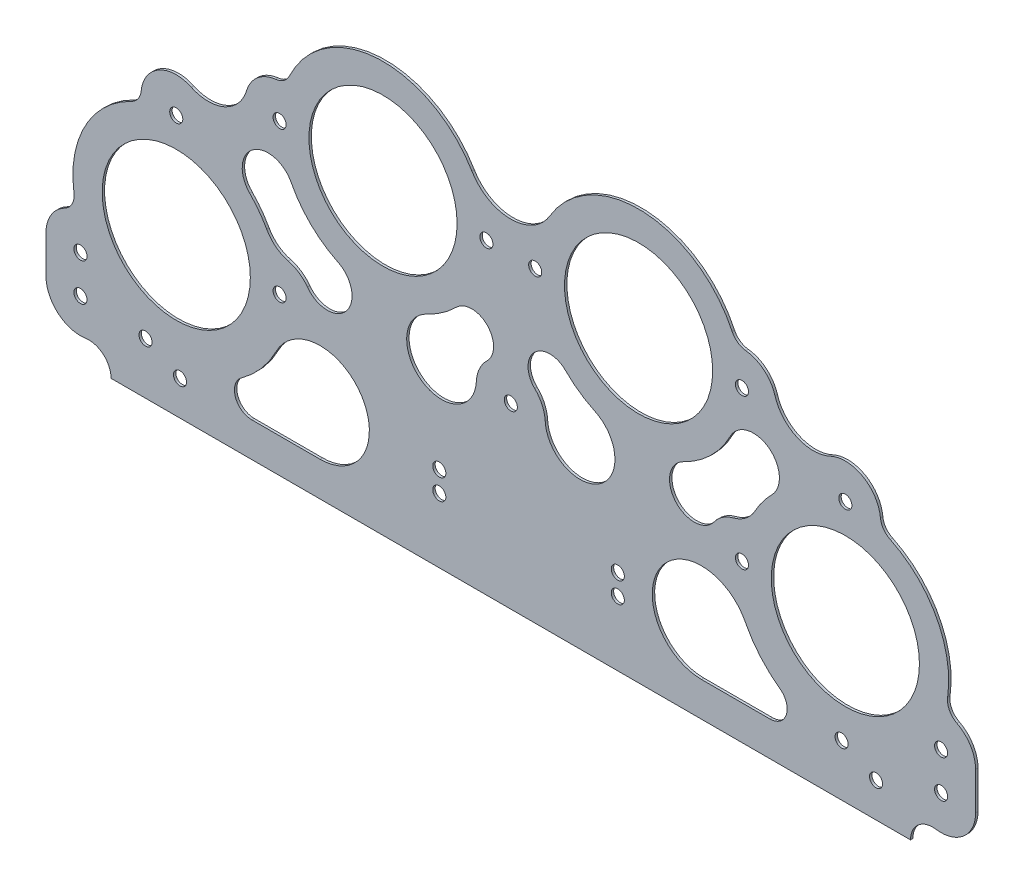
SolidWorks part; units mm, degrees
ref_plane "Front Plane" through (0, 0, 0) normal (0, 0, 1) x (1, 0, 0)
ref_plane "Top Plane" through (0, 0, 0) normal (0, 1, 0) x (1, 0, 0)
ref_plane "Right Plane" through (0, 0, 0) normal (1, 0, 0) x (0, 0, -1)
sketch "Model" plane through (0, 0, 0) normal (0, 0, 1) x (1, 0, 0)
  line L0 (-55.1744, -8.9726) -> (-75.0448, -8.9726)
  line L1 (75.3558, -8.9726) -> (55.4854, -8.9726)
  line L2 (-134.7255, -2.7113) -> (-134.7255, 8.1935)
  line L3 (116.1555, -18.9726) -> (-115.8445, -18.9726)
  line L4 (135.0365, -2.7113) -> (135.0365, 8.1935)
  arc A0 (-70.6765, 41.0853) -> (-75.6107, 47.6717) centre (-96.9265, 26.5616) ccw
  arc A1 (-63.5904, 56.405) -> (-75.6107, 47.6717) centre (-70.2705, 52.9604) ccw
  arc A2 (-63.5904, 56.405) -> (-49.9598, 43.1331) centre (-36.9265, 70.1542) ccw
  arc A3 (-58.8518, 32.4606) -> (-49.9598, 43.1331) centre (-53.0703, 36.6842) ccw
  arc A4 (-58.8518, 32.4606) -> (-64.4265, 36.2441) centre (-66.9265, 26.5616) ccw
  arc A5 (-70.6765, 41.0853) -> (-64.4265, 36.2441) centre (-61.9265, 45.9265) ccw
  arc A6 (-77.9573, 0.0915) -> (-67.9041, 11.7901) centre (-96.9265, 26.5616) ccw
  arc A7 (-55.1744, -8.9726) -> (-67.9041, 11.7901) centre (-55.1744, 5.3111) ccw
  arc A8 (-77.9573, 0.0915) -> (-75.0448, -8.9726) centre (-75.0448, -3.9726) ccw
  arc A9 (-6.7844, 39.9409) -> (-15.6747, 48.9797) centre (-11.1839, 44.5052) ccw
  arc A10 (-6.7844, 39.9409) -> (-9.8306, 33.2688) centre (0.1555, 32.7411) ccw
  arc A11 (-24.2264, 42.975) -> (-9.8306, 33.2688) centre (-19.9405, 33.8029) ccw
  arc A12 (-24.2264, 42.975) -> (-15.6747, 48.9797) centre (-36.9265, 70.1542) ccw
  arc A13 (10.1416, 33.2688) -> (24.5374, 42.975) centre (20.2515, 33.8029) ccw
  arc A14 (10.1416, 33.2688) -> (7.0954, 39.9409) centre (0.1555, 32.7411) ccw
  arc A15 (15.9857, 48.9797) -> (7.0954, 39.9409) centre (11.4949, 44.5052) ccw
  arc A16 (15.9857, 48.9797) -> (24.5374, 42.975) centre (37.2375, 70.1542) ccw
  arc A17 (64.7375, 36.2441) -> (70.9875, 41.0853) centre (62.2375, 45.9265) ccw
  arc A18 (64.7375, 36.2441) -> (59.1628, 32.4606) centre (67.2375, 26.5616) ccw
  arc A19 (50.2707, 43.1331) -> (59.1628, 32.4606) centre (53.3813, 36.6842) ccw
  arc A20 (50.2707, 43.1331) -> (63.9014, 56.405) centre (37.2375, 70.1542) ccw
  arc A21 (75.9217, 47.6717) -> (63.9014, 56.405) centre (70.5815, 52.9604) ccw
  arc A22 (75.9217, 47.6717) -> (70.9875, 41.0853) centre (97.2375, 26.5616) ccw
  circle A23 centre (97.2375, 26.5616) radius 21.5
  circle A24 centre (37.2375, 70.1542) radius 21.5
  circle A25 centre (-36.9265, 70.1542) radius 21.5
  circle A26 centre (-96.9265, 26.5616) radius 21.5
  circle A27 centre (-66.9265, 26.5616) radius 1.8986
  circle A28 centre (-96.9265, 56.5616) radius 1.8986
  circle A29 centre (-66.9265, 70.1542) radius 1.8986
  circle A30 centre (-6.9265, 70.1542) radius 1.8987
  circle A31 centre (7.2375, 70.1542) radius 1.8987
  circle A32 centre (67.2375, 70.1542) radius 1.8987
  circle A33 centre (67.2375, 26.5616) radius 1.8987
  circle A34 centre (97.2375, 56.5616) radius 1.8987
  circle A35 centre (31.2055, 5.7411) radius 1.8987
  circle A36 centre (31.2055, -0.2589) radius 1.8987
  circle A37 centre (-20.5945, 5.7411) radius 1.8986
  circle A38 centre (-20.5945, -0.2589) radius 1.8986
  circle A39 centre (106.1555, -8.9726) radius 1.8987
  circle A40 centre (96.1555, -3.9726) radius 1.8987
  circle A41 centre (-95.8445, -8.9726) radius 1.8987
  circle A42 centre (-105.8445, -3.9726) radius 1.8987
  circle A43 centre (0.1555, 32.7411) radius 1.8986
  circle A44 centre (125.0365, 8.1935) radius 1.8987
  circle A45 centre (125.0365, -2.7113) radius 1.8987
  circle A46 centre (-124.7255, 8.1935) radius 1.8987
  circle A47 centre (-124.7255, -2.7113) radius 1.8987
  arc A48 (68.2151, 11.7901) -> (78.2683, 0.0915) centre (97.2375, 26.5616) ccw
  arc A49 (75.3558, -8.9726) -> (78.2683, 0.0915) centre (75.3558, -3.9726) ccw
  arc A50 (68.2151, 11.7901) -> (55.4854, -8.9726) centre (55.4854, 5.3111) ccw
  arc A51 (126.9276, 22.2604) -> (110.2356, 53.5995) centre (97.2375, 26.5616) ccw
  arc A52 (107.4277, 57.5993) -> (110.2356, 53.5995) centre (112.402, 58.1059) ccw
  arc A53 (107.4277, 57.5993) -> (92.8863, 65.8343) centre (97.2375, 56.5616) ccw
  arc A54 (76.8176, 73.0217) -> (92.8863, 65.8343) centre (87.9498, 76.354) ccw
  arc A55 (76.8176, 73.0217) -> (68.3486, 80.0922) centre (67.2375, 70.1542) ccw
  arc A56 (64.3804, 82.9317) -> (68.3486, 80.0922) centre (68.9042, 85.0613) ccw
  arc A57 (64.3804, 82.9317) -> (11.4402, 85.4674) centre (37.2375, 70.1542) ccw
  arc A58 (-11.1292, 85.4674) -> (11.4402, 85.4674) centre (0.1555, 92.166) ccw
  arc A59 (-11.1292, 85.4674) -> (-64.0694, 82.9317) centre (-36.9265, 70.1542) ccw
  arc A60 (-68.0377, 80.0922) -> (-64.0694, 82.9317) centre (-68.5932, 85.0613) ccw
  arc A61 (-68.0377, 80.0922) -> (-76.5066, 73.0217) centre (-66.9265, 70.1542) ccw
  arc A62 (-92.5753, 65.8343) -> (-76.5066, 73.0217) centre (-87.6388, 76.354) ccw
  arc A63 (-92.5753, 65.8343) -> (-107.1167, 57.5993) centre (-96.9265, 56.5616) ccw
  arc A64 (-109.9246, 53.5995) -> (-107.1167, 57.5993) centre (-112.091, 58.1059) ccw
  arc A65 (-109.9246, 53.5995) -> (-126.6166, 22.2604) centre (-96.9265, 26.5616) ccw
  arc A66 (-129.2851, 17.0935) -> (-126.6166, 22.2604) centre (-131.5649, 21.5435) ccw
  arc A67 (-129.2851, 17.0935) -> (-134.7255, 8.1935) centre (-124.7255, 8.1935) ccw
  arc A68 (-134.7255, -2.7113) -> (-123.2428, -12.6008) centre (-124.7255, -2.7113) ccw
  arc A69 (-115.8445, -18.9726) -> (-123.2428, -12.6008) centre (-122.2875, -18.9726) ccw
  arc A70 (123.5538, -12.6008) -> (116.1555, -18.9726) centre (122.5985, -18.9726) ccw
  arc A71 (123.5538, -12.6008) -> (135.0365, -2.7113) centre (125.0365, -2.7113) ccw
  arc A72 (135.0365, 8.1935) -> (129.5961, 17.0935) centre (125.0365, 8.1935) ccw
  arc A73 (126.9276, 22.2604) -> (129.5961, 17.0935) centre (131.8759, 21.5435) ccw
base flange "Base-Flange1" sketch "Model" thickness 0.7 reverse thickness direction no parameters "D1"=0.8
sketch "Bend-Lines1" [suppressed] plane through (0, 0, 0) normal (0, 1, 0) x (1, 0, 0)
sketch "Bounding-Box1" [suppressed] plane through (0, 0, 0) normal (0, 1, 0) x (1, 0, 0)
sheet metal parameters "Sheet-Metal1" thickness 0.7 parameters "D1"=0.8
flat pattern "Flat-Pattern1" [suppressed]
sketch "Bend-Lines2" plane through (0, 0, 0) normal (0, 1, 0) x (1, 0, 0)
sketch3d "Bounding-Box2" [suppressed]
  line L0 (266.6015, -40.5161, 0) -> (-3.1606, -40.5161, 0) construction
  line L1 (266.6015, 78.6106, 0) -> (-3.1606, 78.6106, 0) construction
  line L2 (266.6015, -40.5161, 0) -> (266.6015, 78.6106, 0) construction
  line L3 (-3.1606, -40.5161, 0) -> (-3.1606, 78.6106, 0) construction
